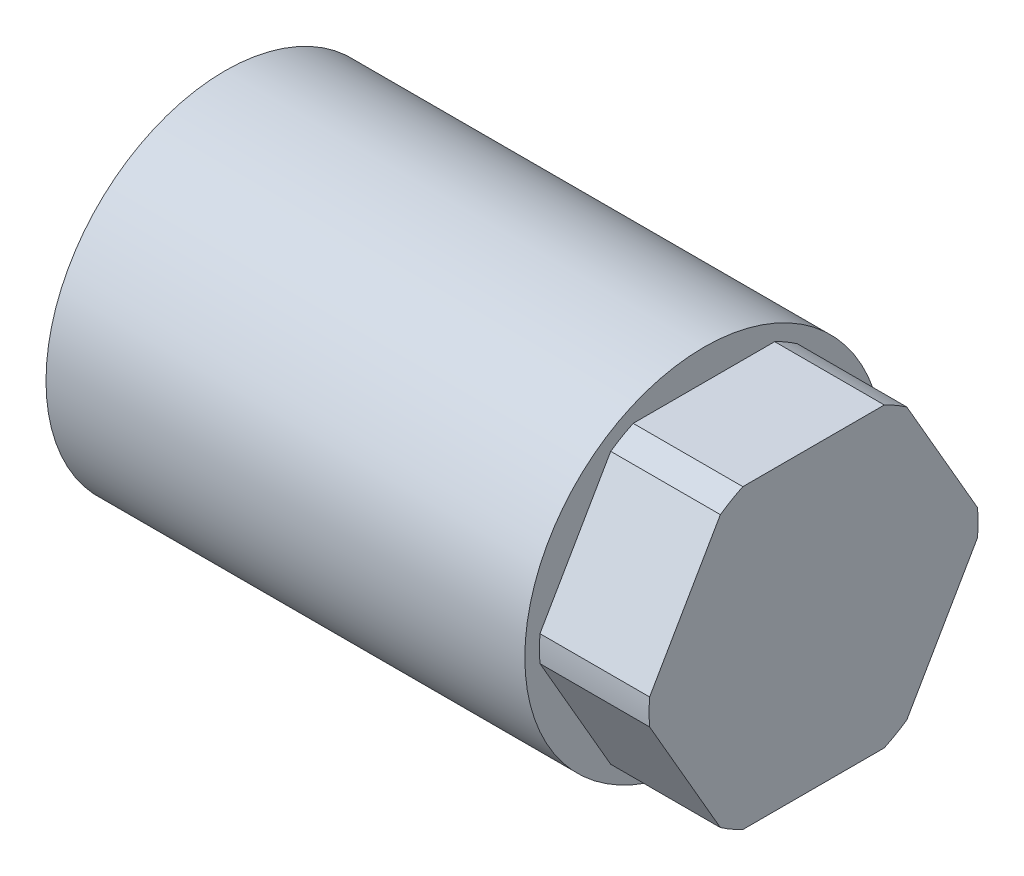
SolidWorks part; units mm, degrees
material "Water"
ref_plane "XY" through (0, 0, 0) normal (0, 0, 1) x (1, 0, 0)
ref_plane "XZ" through (0, 0, 0) normal (0, 1, 0) x (1, 0, 0)
ref_plane "YZ" through (0, 0, 0) normal (1, 0, 0) x (0, 0, -1)
ref_axis "X" through (-88.99, 0, 0) along (1, 0, 0)
ref_axis "Y" through (0, -55, 0) along (0, 1, 0)
ref_axis "Z" through (0, 0, 55) along (0, 0, -1)
sketch "Sketch1" plane through (0, 0, 0) normal (0, 0, 1) x (1, 0, 0)
  line L0 (0, 0) -> (0, 6.35) construction
  line L1 (0, 11.43) -> (-7.62, 11.43)
  line L2 (-7.62, 11.43) -> (-7.62, 12.446)
  line L3 (-7.62, 12.446) -> (-40.894, 12.446)
  line L4 (-40.894, 12.446) -> (-40.894, 0)
  line L5 (-40.894, 0) -> (19.05, 0)
  line L6 (19.05, 0) -> (19.05, 6.35)
  line L7 (19.05, 6.35) -> (0, 6.35)
  line L8 (0, 6.35) -> (0, 11.43)
  dimension "D1" = 40.894
  dimension "D2" = 6.35
  dimension "D3" = 12.446
  dimension "D4" = 11.43
  dimension "D5" = 7.62
  dimension "D6" = 19.05
revolve "Revolve1" add sketch "Sketch1" angle 360 about L5
sketch "Sketch3" plane through (0, 0, 0) normal (1, 0, 0) x (0, 0, -1)
  line L1 (5.9575, 10.3188) -> (-5.9575, 10.3188)
  line L2 (-5.9575, 10.3188) -> (-11.9151, 0)
  line L3 (-11.9151, 0) -> (-5.9575, -10.3188)
  line L4 (-5.9575, -10.3188) -> (5.9575, -10.3188)
  line L5 (5.9575, -10.3188) -> (11.9151, 0)
  line L6 (11.9151, 0) -> (5.9575, 10.3188)
  circle A0 centre (0, 0) radius 10.3188 construction
  dimension "D1" = 20.6375
extrude "Cut-Extrude5" cut sketch "Sketch3" against normal up to surface (7.62 mm away) flip side to cut up to face at (-7.62, -12.446, 0)
sketch "Sketch4" plane through (0, 0, 0) normal (1, 0, 0) x (0, 0, -1)
  circle A0 centre (0, 0) radius 6.35 construction
  circle A1 centre (0, 0) radius 6.35
extrude "Cut-Extrude6" cut sketch "Sketch4" along normal through all
